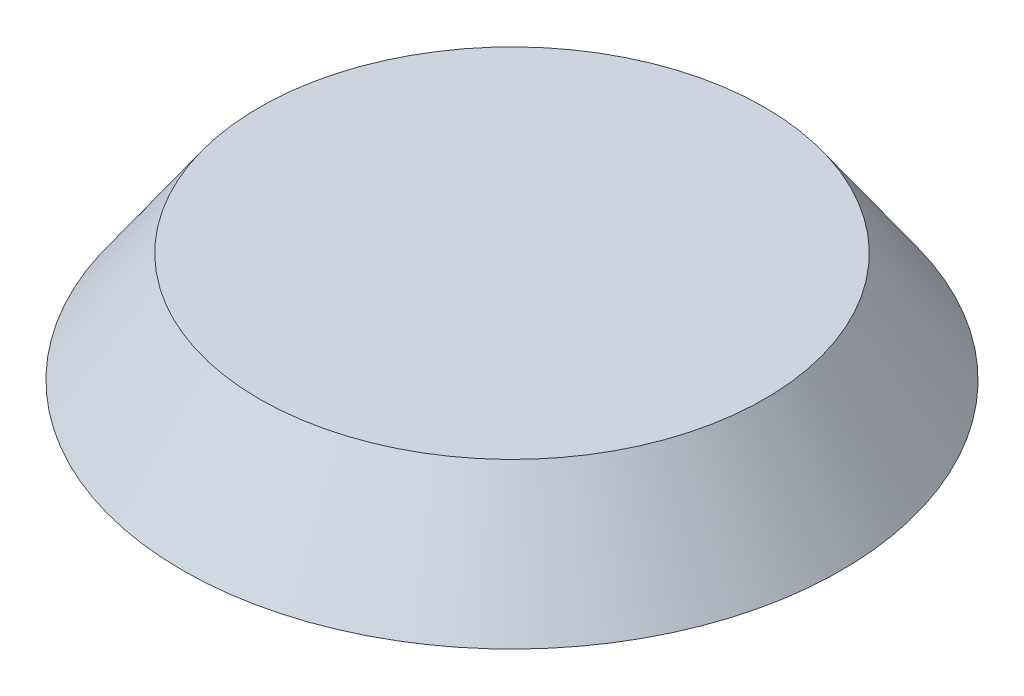
SolidWorks part; units mm, degrees
ref_plane "Plan de face" through (0, 0, 0) normal (0, 0, 1) x (1, 0, 0)
ref_plane "Plan de dessus" through (0, 0, 0) normal (0, 1, 0) x (1, 0, 0)
ref_plane "Plan de droite" through (0, 0, 0) normal (1, 0, 0) x (0, 0, -1)
sketch "Esquisse1" plane through (0, 0, 0) normal (0, 1, 0) x (1, 0, 0)
  circle A0 centre (0, 0) radius 30
  dimension "D1" = 60
extrude "Boss.-Extru.1" add sketch "Esquisse1" along normal blind 10 contours A0
chamfer "Chanfrein1" distance 10 angle 35 1 edges at (0, 10, 30) first distance on face at (0, 10, 30)
shell "Coque2" thickness 1.5 removed face at (0, 0, 30)
sketch "Esquisse2" plane through (0, 8.5, 0) normal (0, -1, 0) x (1, 0, 0)
  circle A0 centre (-16, 0) radius 4
  dimension "D2" = 8
  dimension "D1" = 16
extrude "Boss.-Extru.2" add sketch "Esquisse2" along normal blind 8.5
chamfer "Chanfrein2" distance 8.5 angle 3 1 edges at (-16, 0, -4) first distance on face at (-16, 0, -4)
sketch "Esquisse5" plane through (0, 0, 0) normal (0, -1, 0) x (1, 0, 0)
  circle A0 centre (-16, 0) radius 2.5545
  circle A1 centre (-16, 0) radius 3.5545 construction
  dimension "D1" = 1
  dimension "D2" = 5.1091
extrude "Enlèv. mat.-Extru.1" cut sketch "Esquisse5" against normal blind 8.5
pattern_circular "Répétition circulaire1" count 3 over 360 about axis through (0, 8.5, 0) along (0, 1, 0) of "Boss.-Extru.2", "Chanfrein2", "Enlèv. mat.-Extru.1"
